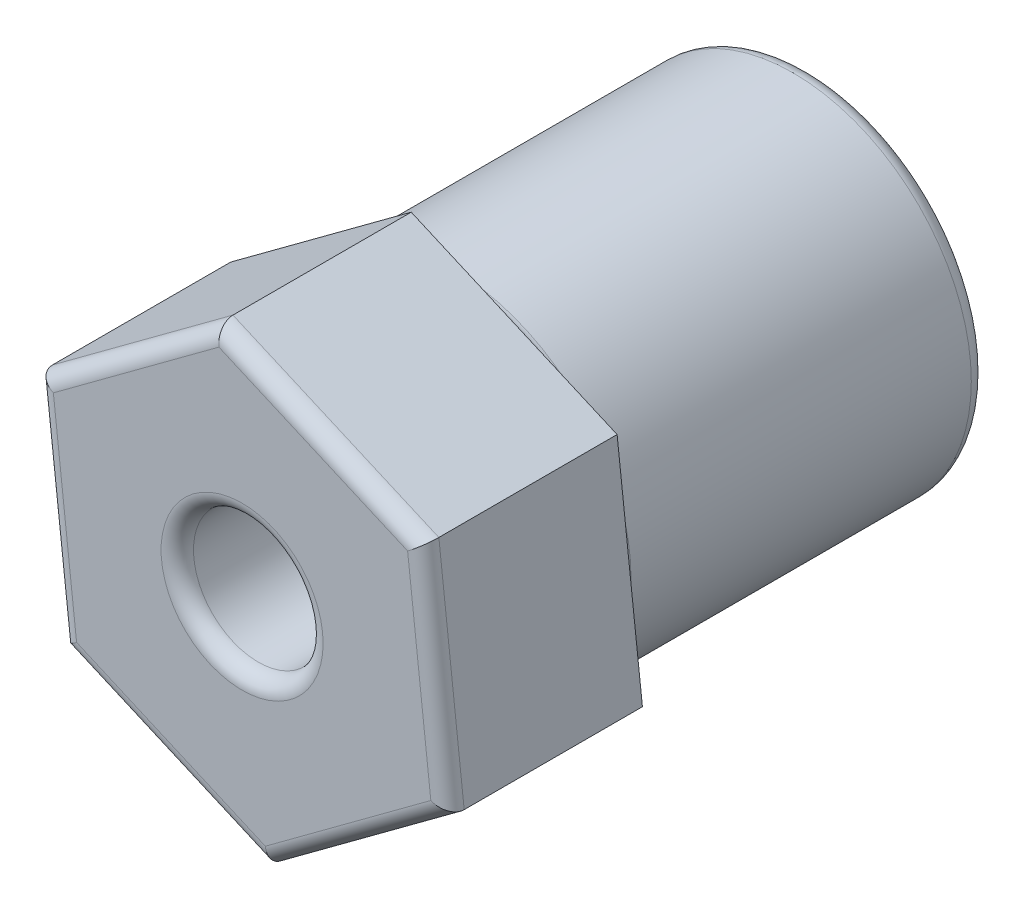
SolidWorks part; units mm, degrees
ref_plane "前视基准面" through (0, 0, 0) normal (0, 0, 1) x (1, 0, 0)
ref_plane "上视基准面" through (0, 0, 0) normal (0, 1, 0) x (1, 0, 0)
ref_plane "右视基准面" through (0, 0, 0) normal (1, 0, 0) x (0, 0, -1)
sketch "草图1" plane through (0, 0, 0) normal (0, 0, 1) x (1, 0, 0)
  line L1 (-6.3524, 2.7652) -> (-5.571, -4.1187)
  line L2 (-5.571, -4.1187) -> (0.7814, -6.884)
  line L3 (0.7814, -6.884) -> (6.3524, -2.7652)
  line L4 (6.3524, -2.7652) -> (5.571, 4.1187)
  line L5 (5.571, 4.1187) -> (-0.7814, 6.884)
  line L6 (-0.7814, 6.884) -> (-6.3524, 2.7652)
  circle A0 centre (0, 0) radius 6 construction
  dimension "D2" = 12
extrude "凸台-拉伸1" add sketch "草图1" along normal blind 6
sketch "草图2" plane through (0, 0, 0) normal (0, 0, 1) x (1, 0, 0)
  circle A0 centre (0, 0) radius 5.5
  dimension "D1" = 11
extrude "凸台-拉伸2" add sketch "草图2" against normal blind 11.5
sketch "草图3" plane through (0, 0, -11.5) normal (0, 0, -1) x (-1, 0, 0)
  circle A0 centre (0, 0) radius 2
  dimension "D1" = 4
extrude "切除-拉伸1" cut sketch "草图3" against normal up to surface (17.5 mm away) up to face at (0, 0, 6)
fillet "圆角1" radius 0.5 1 edges at (5.5, 0, 0)
fillet "圆角2" radius 0.5 7 edges at (3.5669, -4.8246, 6) (-2.3948, -5.5014, 6) (-5.9617, -0.6767, 6) (-3.5669, 4.8246, 6) (2.3948, 5.5014, 6) (5.9617, 0.6767, 6) (5.5, 0, -11.5)
fillet "圆角3" radius 0.5 2 edges at (-2, 0, -11.5) (2, 0, 6)
